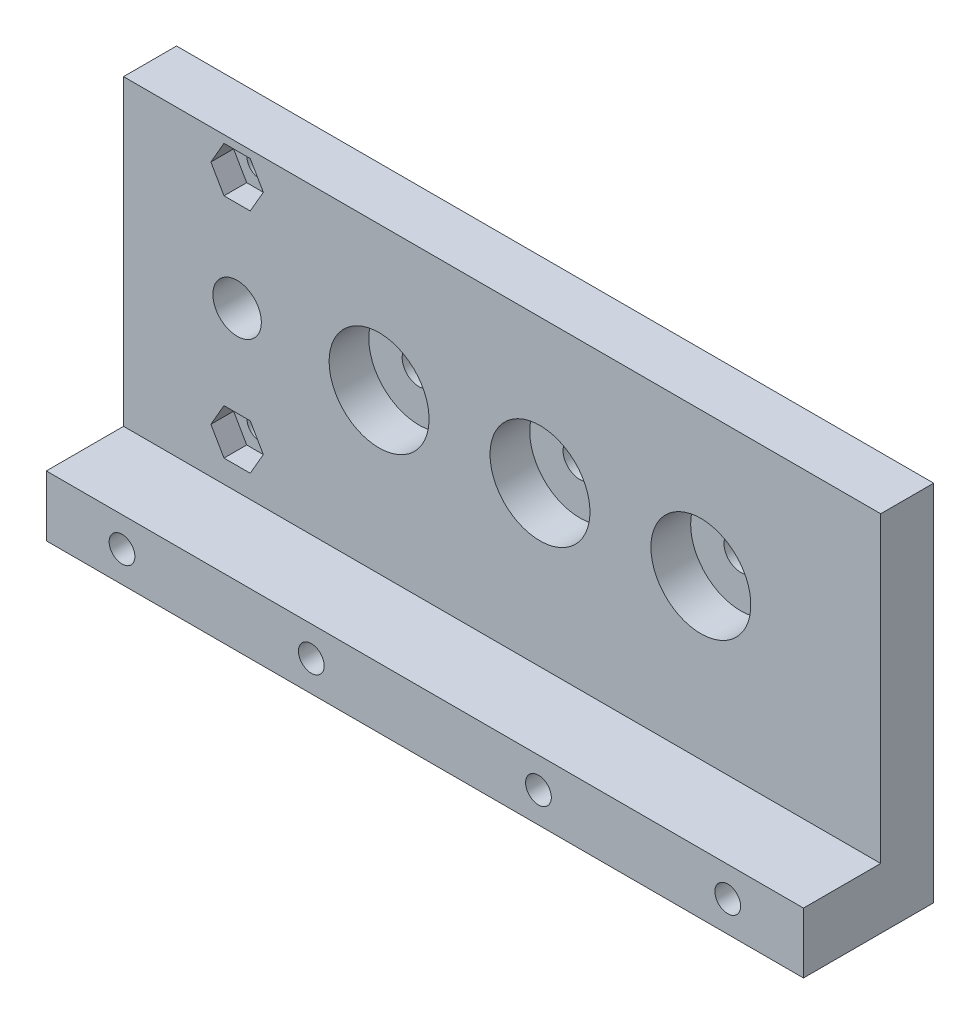
SolidWorks part; units mm, degrees
ref_plane "Front Plane" through (0, 0, 0) normal (0, 0, 1) x (1, 0, 0)
ref_plane "Top Plane" through (0, 0, 0) normal (0, 1, 0) x (1, 0, 0)
ref_plane "Right Plane" through (0, 0, 0) normal (1, 0, 0) x (0, 0, -1)
sketch "Sketch1" plane through (0, 0, 0) normal (0, 0, 1) x (1, 0, 0)
  line L1 (0, 0) -> (100, 0)
  line L2 (0, 0) -> (0, 48)
  line L3 (0, 48) -> (100, 48)
  line L4 (100, 0) -> (100, 48)
  dimension "D1" = 100
  dimension "D2" = 48
extrude "Boss-Extrude1" add sketch "Sketch1" along normal blind 7
sketch "Sketch2" plane through (0, 0, 7) normal (0, 0, 1) x (1, 0, 0)
  line L0 (0, 0) -> (100, 0) construction
  line L1 (0, 48) -> (0, 0) construction
  circle A0 centre (15, 29) radius 3.2
  circle A1 centre (33.75, 29) radius 2.2
  circle A2 centre (55, 29) radius 2.2
  circle A3 centre (76.25, 29) radius 2.2
  dimension "D1" = 4.4
  dimension "D2" = 18.75
  dimension "D3" = 21.25
  dimension "D4" = 21.25
  dimension "D5" = 29
  dimension "D6" = 15
  dimension "D7" = 6.4
extrude "Cut-Extrude1" cut sketch "Sketch2" against normal up to next
sketch "Sketch3" plane through (0, 0, 0) normal (0, 0, -1) x (-1, 0, 0)
  line L0 (0, 48) -> (0, 0) construction
  line L1 (-100, 0) -> (0, 0)
  line L2 (-100, 0) -> (-100, 8)
  line L3 (-100, 8) -> (0, 8)
  line L4 (0, 0) -> (0, 8)
  dimension "D1" = 8
extrude "Boss-Extrude2" add sketch "Sketch3" along normal blind 10.2
sketch "Sketch4" plane through (0, 0, 0) normal (0, 0, -1) x (-1, 0, 0)
  circle A0 centre (-76.25, 29) radius 6.6
  circle A1 centre (-55, 29) radius 6.6
  circle A2 centre (-33.75, 29) radius 6.6
  dimension "D1" = 13.2
extrude "Cut-Extrude2" cut sketch "Sketch4" against normal blind 5.25
sketch "Sketch5" plane through (0, 0, 7) normal (0, 0, 1) x (1, 0, 0)
  line L0 (35, 4.0521) -> (65, 4) construction
  line L1 (0, 0) -> (100, 0) construction
  circle A0 centre (35, 4.0521) radius 2.6
  circle A1 centre (65, 4) radius 2.6
  point P6 (50, 0)
  point P7 (50, 4.0261)
  dimension "D1" = 5.2
  dimension "D2" = 30
  dimension "D3" = 4
extrude "Cut-Extrude3" cut sketch "Sketch5" against normal blind 7
sketch "Sketch7" plane through (0, 0, 0) normal (0, 0, 1) x (1, 0, 0)
  circle A0 centre (35, 4.0521) radius 1.7
  circle A1 centre (65, 4) radius 1.7
  dimension "D1" = 3.4
extrude "Cut-Extrude4" cut sketch "Sketch7" against normal through all
sketch "Sketch8" plane through (0, 0, 7) normal (0, 0, 1) x (1, 0, 0)
  line L0 (10, 4.0521) -> (35, 4.0521) construction
  line L1 (0, 48) -> (0, 0) construction
  line L2 (100, 0) -> (100, 48) construction
  circle A0 centre (10, 4.0521) radius 1.7
  circle A1 centre (90, 4.0521) radius 1.7
  dimension "D1" = 3.4
  dimension "D2" = 10
  dimension "D3" = 10
extrude "Cut-Extrude5" cut sketch "Sketch8" against normal up to next
mirror "Mirror1" about plane through (0, 0, -10.2) normal (0, 0, 1) of bodies 110
delete or keep bodies "Body-Delete/Keep 1" type delete bodies bodies 110
sketch "Sketch9" plane through (0, 0, -27.4) normal (0, 0, -1) x (-1, 0, 0)
  line L1 (-88.2679, 1.0521) -> (-86.5359, 4.0521)
  line L2 (-86.5359, 4.0521) -> (-88.2679, 7.0521)
  line L3 (-88.2679, 7.0521) -> (-91.7321, 7.0521)
  line L4 (-91.7321, 7.0521) -> (-93.4641, 4.0521)
  line L5 (-93.4641, 4.0521) -> (-91.7321, 1.0521)
  line L6 (-91.7321, 1.0521) -> (-88.2679, 1.0521)
  line L7 (-13.4641, 4.0521) -> (-11.7321, 1.0521)
  line L8 (-11.7321, 1.0521) -> (-8.2679, 1.0521)
  line L9 (-8.2679, 1.0521) -> (-6.5359, 4.0521)
  line L10 (-6.5359, 4.0521) -> (-8.2679, 7.0521)
  line L11 (-8.2679, 7.0521) -> (-11.7321, 7.0521)
  line L12 (-11.7321, 7.0521) -> (-13.4641, 4.0521)
  circle A0 centre (-90, 4.0521) radius 3 construction
  circle A1 centre (-10, 4.0521) radius 3 construction
  dimension "D1" = 6
extrude "Cut-Extrude6" cut sketch "Sketch9" against normal blind 3
sketch "Sketch10" plane through (0, 0, -27.4) normal (0, 0, -1) x (-1, 0, 0)
  line L0 (-15, 44) -> (-15, 29) construction
  circle A0 centre (-15, 44) radius 1.7
  circle A1 centre (-15, 14) radius 1.7
  dimension "D1" = 3.4
  dimension "D2" = 30
  dimension "D3" = 15
extrude "Cut-Extrude7" cut sketch "Sketch10" against normal up to next
sketch "Sketch11" plane through (0, 0, -20.4) normal (0, 0, 1) x (1, 0, 0)
  line L1 (18.4641, 44) -> (16.7321, 47)
  line L2 (16.7321, 47) -> (13.2679, 47)
  line L3 (13.2679, 47) -> (11.5359, 44)
  line L4 (11.5359, 44) -> (13.2679, 41)
  line L5 (13.2679, 41) -> (16.7321, 41)
  line L6 (16.7321, 41) -> (18.4641, 44)
  line L7 (18.4641, 14) -> (16.7321, 17)
  line L8 (16.7321, 17) -> (13.2679, 17)
  line L9 (13.2679, 17) -> (11.5359, 14)
  line L10 (11.5359, 14) -> (13.2679, 11)
  line L11 (13.2679, 11) -> (16.7321, 11)
  line L12 (16.7321, 11) -> (18.4641, 14)
  circle A0 centre (15, 44) radius 3 construction
  circle A1 centre (15, 14) radius 3 construction
  dimension "D1" = 6
extrude "Cut-Extrude8" cut sketch "Sketch11" against normal blind 3
